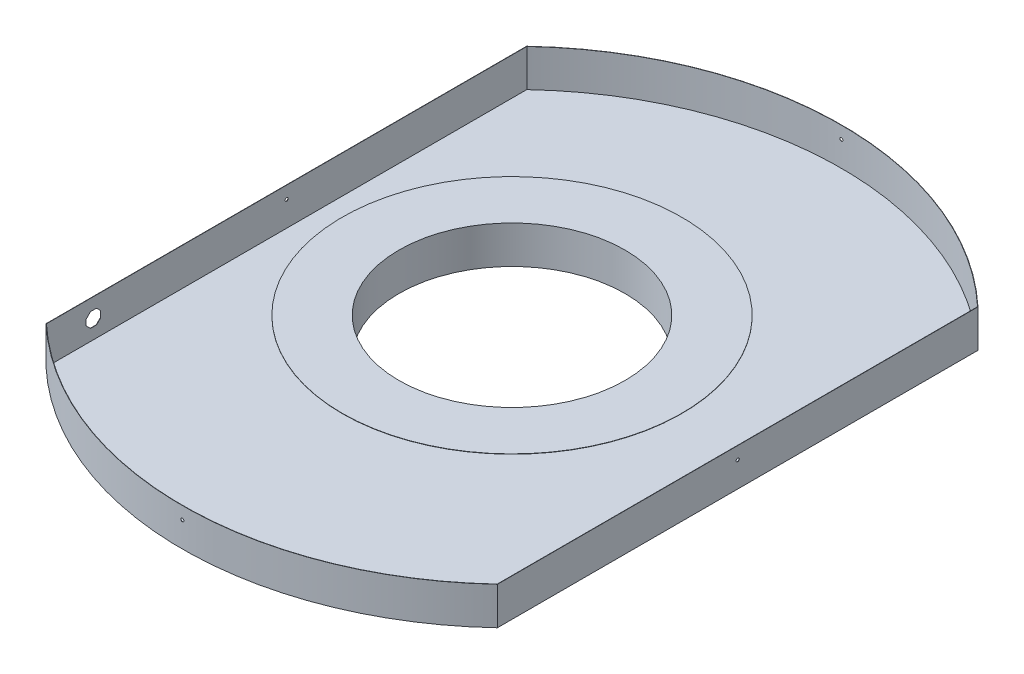
SolidWorks part; units mm, degrees
material "1345 Alloy"
ref_plane "Front Plane" through (0, 0, 0) normal (0, 0, 1) x (1, 0, 0)
ref_plane "Top Plane" through (0, 0, 0) normal (0, 1, 0) x (1, 0, 0)
ref_plane "Right Plane" through (0, 0, 0) normal (1, 0, 0) x (0, 0, -1)
sketch "Sketch1" plane through (0, 0, 0) normal (0, 1, 0) x (1, 0, 0)
  circle A0 centre (0, 0) radius 1750
extrude "Boss-Extrude1" add sketch "Sketch1" along normal blind 500
sketch "Sketch2" plane through (0, 500, 0) normal (0, 1, 0) x (1, 0, 0)
  circle A0 centre (0, 0) radius 900
extrude "Cut-Extrude2" cut sketch "Sketch2" against normal blind 300
sketch "Sketch10" plane through (0, 500, 0) normal (0, 1, 0) x (1, 0, 0)
  line L1 (-2200.588, -2811.5432) -> (2200.588, -2811.5432)
  line L2 (-2200.588, -2811.5432) -> (-2200.588, 2811.5432)
  line L3 (-2200.588, 2811.5432) -> (2200.588, 2811.5432)
  line L4 (2200.588, -2811.5432) -> (2200.588, 2811.5432)
  line L5 (-2200.588, -2811.5432) -> (2200.588, 2811.5432) construction
  line L6 (-2200.588, 2811.5432) -> (2200.588, -2811.5432) construction
  line L7 (-1198.0599, -2169.9586) -> (1198.0599, -2169.9586)
  line L8 (-1198.0599, -2169.9586) -> (-1198.0599, 2169.9586)
  line L9 (-1198.0599, 2169.9586) -> (1198.0599, 2169.9586)
  line L10 (1198.0599, -2169.9586) -> (1198.0599, 2169.9586)
  line L11 (-1198.0599, -2169.9586) -> (1198.0599, 2169.9586) construction
  line L12 (-1198.0599, 2169.9586) -> (1198.0599, -2169.9586) construction
  point P0 (0, 0)
  point P6 (0, 0)
extrude "Cut-Extrude10" cut sketch "Sketch10" against normal through all both and the other way through all
sketch "Sketch3" plane through (0, 0, 0) normal (0, -1, 0) x (1, 0, 0)
  circle A0 centre (0, 0) radius 600
extrude "Cut-Extrude3" cut sketch "Sketch3" against normal blind 300
shell "Shell1" thickness 1.5 removed face at (0, 500, 900)
sketch "Sketch11" plane through (0, 200, 0) normal (0, 1, 0) x (1, 0, 0)
  line L1 (-1546.6788, 2430.4952) -> (1546.6788, 2430.4952)
  line L2 (-1546.6788, 2430.4952) -> (-1546.6788, -2430.4952)
  line L3 (-1546.6788, -2430.4952) -> (1546.6788, -2430.4952)
  line L4 (1546.6788, 2430.4952) -> (1546.6788, -2430.4952)
  line L5 (-1546.6788, 2430.4952) -> (1546.6788, -2430.4952) construction
  line L6 (-1546.6788, -2430.4952) -> (1546.6788, 2430.4952) construction
  point P0 (0, 0)
extrude "Cut-Extrude11" cut sketch "Sketch11" along normal through all
ref_plane "Plane1" through (0, 0, 2000) normal (0, 0, 1) x (1, 0, 0)
sketch "Sketch7" plane through (0, 0, 2000) normal (0, 0, 1) x (1, 0, 0)
  circle A0 centre (0, 133.8976) radius 8.382
extrude "Cut-Extrude6" cut sketch "Sketch7" against normal blind 900
pattern_circular "CirPattern1" count 4 over 360 about axis through (0, 500, 0) along (0, -1, 0) of "Cut-Extrude6" reverse direction yes
ref_plane "Plane2" through (-1237.4369, 0, 1237.4369) normal (-0.7071, 0, 0.7071) x (0, -1, 0)
sketch "Sketch12" plane through (-1198.0599, 0, 0) normal (-1, 0, 0) x (0, 0, 1)
  line L0 (986.4823, 84.2757) -> (1009.035, 61.7229)
  line L1 (1009.035, 61.7229) -> (1040.9295, 61.7229)
  line L2 (1040.9295, 61.7229) -> (1063.4823, 84.2757)
  line L3 (1063.4823, 84.2757) -> (1063.4823, 116.1701)
  line L4 (1063.4823, 116.1701) -> (1040.9295, 138.7229)
  line L5 (1040.9295, 138.7229) -> (1009.035, 138.7229)
  line L6 (1009.035, 138.7229) -> (986.4823, 116.1701)
  line L7 (986.4823, 116.1701) -> (986.4823, 84.2757)
  circle A0 centre (1024.9823, 100.2229) radius 38.5 construction
  point P10 (0, 0)
  point P11 (0, 0)
  point P12 (0, 0)
  point P13 (0, 0)
  point P14 (0, 0)
  point P15 (0, 0)
  point P16 (0, 0)
extrude "Cut-Extrude13" cut sketch "Sketch12" against normal blind 10
